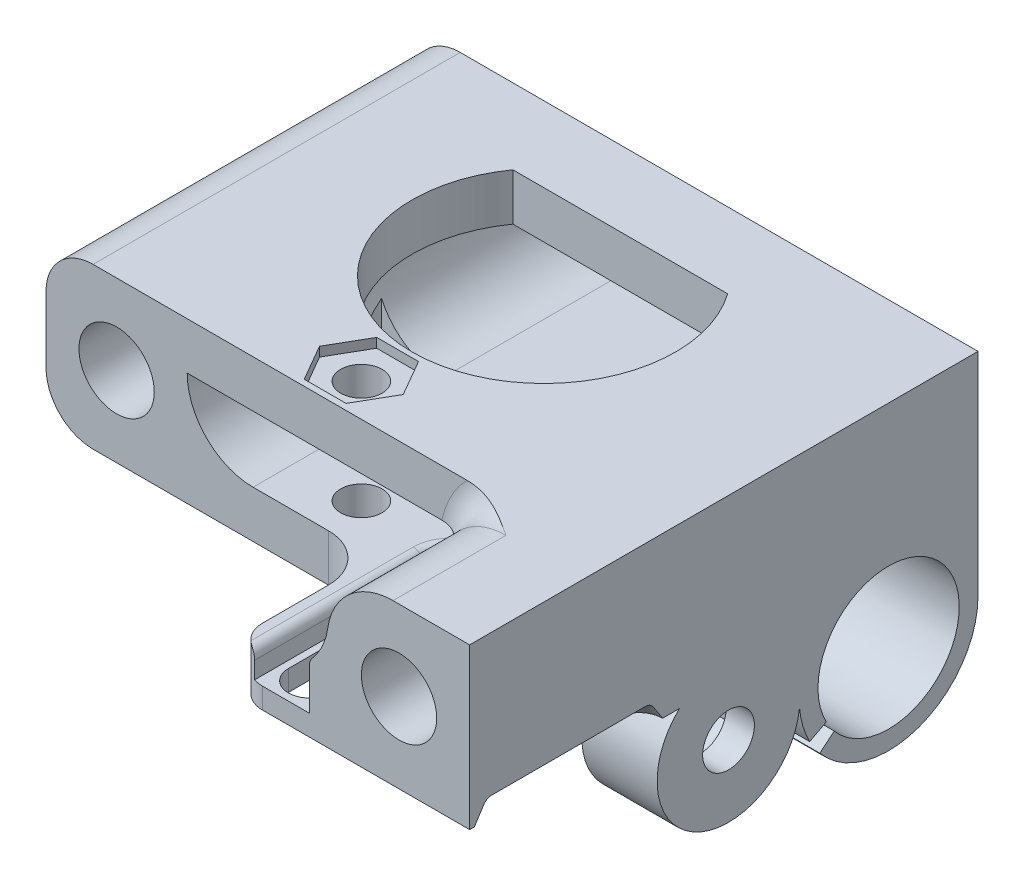
SolidWorks part; units mm, degrees
material "ABS generico"
ref_plane "Front Plane" through (0, 0, 0) normal (0, 0, 1) x (1, 0, 0)
ref_plane "Top Plane" through (0, 0, 0) normal (0, 1, 0) x (1, 0, 0)
ref_plane "Right Plane" through (0, 0, 0) normal (1, 0, 0) x (0, 0, -1)
sketch "Sketch1" plane through (0, 0, 0) normal (1, 0, 0) x (0, 0, -1)
  line L1 (21.1236, -26.9641) -> (22.8813, -26.0274)
  line L3 (23.7305, -27.2923) -> (22.1984, -28.5649)
  line L4 (20.0416, -23.294) -> (20.0416, -17)
  line L8 (39, 0) -> (0, 0)
  line L12 (0, -17) -> (0, 0)
  line L13 (0, -17) -> (20.0416, -17)
  line L15 (39, -22.5) -> (39, 0)
  line L19 (16.5, -29.4282) -> (20.0416, -23.294) construction
  line L20 (8.5, -29.4282) -> (16.5, -29.4282) construction
  line L21 (4.5, -22.5) -> (8.5, -29.4282) construction
  line L22 (4.5, -17) -> (4.5, -22.5) construction
  arc A0 (23.7305, -27.2923) -> (22.8813, -26.0274) centre (29.5041, -22.4988) ccw
  arc A1 (20.0416, -23.294) -> (21.1236, -26.9641) centre (29.5041, -22.4988) ccw
  arc A2 (22.1984, -28.5649) -> (39, -22.5) centre (29.5041, -22.4988) ccw
  circle A5 centre (12.5, -22.5) radius 2.75 construction
  dimension "D2" = 7.5042
  dimension "D3" = 9.4959
  dimension "D1" = 39
  dimension "D4" = 17
extrude "Extrude1" add sketch "Sketch1" against normal blind 60
sketch "Sketch2" plane through (0, 0, 0) normal (0, 0, 1) x (1, 0, 0)
  line L0 (-60, -8.5) -> (0, -8.5) construction
  line L1 (-60, 0) -> (-60, -17) construction
  line L2 (0, 0) -> (0, -17) construction
  line L3 (-30, 1.8171) -> (-30, -40.9837) construction
  line L5 (-15, -12) -> (-45, -12)
  line L6 (-15, -12) -> (-15, -5)
  line L7 (-15, -5) -> (-45, -5)
  line L8 (-45, -12) -> (-45, -5)
  line L9 (-15, -12) -> (-45, -5) construction
  line L10 (-15, -5) -> (-45, -12) construction
  circle A0 centre (-52.5, -8.5) radius 4
  circle A1 centre (-7.5, -8.5) radius 4
  point P12 (-30, -8.5)
  dimension "D1" = 8
  dimension "D2" = 22.5
  dimension "D3" = 7.5
  dimension "D4" = 7
  dimension "D5" = 30
extrude "Extrude2" cut sketch "Sketch2" against normal up to surface (39 mm away) up to face at (-30, -11.25, -39)
sketch "Sketch3" plane through (0, 0, 0) normal (0, 0, 1) x (1, 0, 0)
  line L0 (-52.5, -8.5) -> (-7.5, -8.5) construction
  line L1 (-52.5, -8.5) -> (-52.5, 8.8734) construction
  line L2 (-32.5, -8.5) -> (-32.5, 8.8734) construction
  dimension "D1" = 20
sketch "Sketch4" plane through (0, 0, 0) normal (1, 0, 0) x (0, 0, -1)
  line L0 (7.2804, -17) -> (20.0416, -17)
  line L1 (12.5, -17.9967) -> (8.6, -20.2483) construction
  line L2 (8.6, -20.2483) -> (8.6, -24.7517) construction
  line L3 (8.6, -24.7517) -> (12.5, -27.0033) construction
  line L4 (12.5, -27.0033) -> (16.4, -24.7517) construction
  line L5 (16.4, -24.7517) -> (16.4, -20.2483) construction
  line L6 (16.4, -20.2483) -> (12.5, -17.9967) construction
  line L7 (0, -17) -> (20.0416, -17) construction
  line L8 (20.0416, -17) -> (20.0817, -22.3872)
  circle A0 centre (12.5, -22.5) radius 3.9 construction
  arc A1 (7.2804, -17) -> (20.0817, -22.3872) centre (12.5, -22.5) ccw
  dimension "D1" = 7.8
extrude "Extrude3" add sketch "Sketch4" against normal blind 8
sketch "Sketch5" plane through (0, 0, 0) normal (1, 0, 0) x (0, 0, -1)
  circle A0 centre (12.5, -22.5) radius 2.75
  dimension "D1" = 5.5
extrude "Extrude4" cut sketch "Sketch5" against normal up to surface (8 mm away) up to face at (-8, -22.1484, -14.2839)
sketch "Sketch6" plane through (-8, 0, 0) normal (-1, 0, 0) x (0, 0, 1)
  line L1 (-12.5, -17.8812) -> (-16.5, -20.1906)
  line L2 (-16.5, -20.1906) -> (-16.5, -24.8094)
  line L3 (-16.5, -24.8094) -> (-12.5, -27.1188)
  line L4 (-12.5, -27.1188) -> (-8.5, -24.8094)
  line L5 (-8.5, -24.8094) -> (-8.5, -20.1906)
  line L6 (-8.5, -20.1906) -> (-12.5, -17.8812)
extrude "Extrude5" cut sketch "Sketch6" against normal blind 5
sketch "Sketch7" plane through (0, 0, 0) normal (0, 1, 0) x (1, 0, 0)
  line L2 (-31, -370.8295) -> (-31, 97.9462) construction
  line L6 (-30.9897, -180.6724) -> (-30.9897, -405.4164) construction
  circle A0 centre (-31, 4.5) radius 2.2
extrude "Extrude6" cut sketch "Sketch7" against normal up to surface (17 mm away) up to face at (-22.6667, -17, -9.1073)
sketch "Sketch8" plane through (0, 0, -39) normal (0, 0, -1) x (-1, 0, 0)
  line L0 (7.5, -8.5) -> (52.5, -8.5) construction
  line L1 (30, -8.5) -> (30, 3.0319) construction
  circle A0 centre (7.5, -8.5) radius 4.201
  circle A1 centre (52.5, -8.5) radius 1.25
  circle A2 centre (7.5, -8.5) radius 1.25
  circle A3 centre (52.5, -8.5) radius 4.201
  dimension "D1" = 2.5
extrude "Extrude7" add sketch "Sketch8" against normal blind 5
sketch "Sketch10" plane through (-60, 0, 0) normal (-1, 0, 0) x (0, 0, 1)
  line L1 (-20.0416, -17) -> (-39.247, -17)
  line L2 (-20.0416, -17) -> (-20.0416, -32.1139)
  line L3 (-20.0416, -32.1139) -> (-39.247, -32.1139)
  line L4 (-39.247, -17) -> (-39.247, -32.1139)
extrude "Extrude8" cut sketch "Sketch10" against normal blind 10
fillet "Fillet9" radius 10 2 edges at (-55, -17, -24.3976) (-55, -17, -34.6107)
fillet "Fillet11" radius 5 1 edges at (-60, 0, -19.5)
fillet "Fillet12" radius 5 5 edges at (-60, -17, -38.3198) (-60, -16.7094, -35.2462) (-60, -14.9946, -29.5041) (-60, -16.7094, -23.7621) (-60, -17, -10.6843)
sketch "Sketch12" plane through (0, 0, 0) normal (0, 0, 1) x (1, 0, 0)
  line L0 (-15, -12) -> (-15, 2.5343) construction
  line L1 (0, 0) -> (-20.7492, 0) construction
  line L2 (-55, 0) -> (0, 0) construction
  line L3 (-45, -12) -> (-15, -12) construction
  line L4 (-15, 0) -> (0, 0)
  line L5 (-11.5, -8.5) -> (-11.5, 2.5343) construction
  line L6 (-15, -17) -> (0, -17)
  line L7 (0, 0) -> (0, -17)
  line L8 (-15, -17) -> (-25, -17)
  line L9 (-25, -12) -> (-15, -12)
  line L10 (-15, -12) -> (-15, 0)
  line L11 (-25, -17) -> (-25, -12)
  circle A0 centre (-7.5, -8.5) radius 4
  point P21 (-14.5, -8.5)
  point P22 (-14.5, 2.5343)
  dimension "D3" = 8
  dimension "D1" = 10
extrude "Extrude10" add sketch "Sketch12" along normal blind 15
sketch "Sketch13" plane through (0, -17, 0) normal (0, -1, 0) x (1, 0, 0)
  line L2 (-20, -5.2455) -> (-20, 23.7024) construction
  line L4 (-25, 0) -> (-9.3359, 0) construction
  line L5 (-25, 15) -> (-25, 0) construction
  line L6 (-20, 12) -> (-20, -3) construction
  line L7 (-17.75, 12) -> (-17.75, -3)
  line L8 (-22.25, 12) -> (-22.25, -3)
  line L9 (-25, 15) -> (0, 15) construction
  arc A0 (-17.75, 12) -> (-22.25, 12) centre (-20, 12) ccw
  arc A1 (-22.25, -3) -> (-17.75, -3) centre (-20, -3) ccw
  point P14 (-20, 4.5)
  dimension "D2" = 3
  dimension "D1" = 5
extrude "Extrude11" cut sketch "Sketch13" against normal up to surface (5 mm away) up to face at (-28.8, -12, -4.5)
sketch "Sketch14" plane through (0, -17, 0) normal (0, -1, 0) x (1, 0, 0)
  line L0 (1.5, -3) -> (1.5, 12)
  line L1 (-12, -10.2024) -> (-12, 22.3262) construction
  line L2 (-1.5, 12) -> (-1.5, -3)
  line L3 (-10.5, -3) -> (-10.5, 12)
  line L4 (-13.5, 12) -> (-13.5, -3)
  arc A0 (-1.5, -3) -> (1.5, -3) centre (0, -3) ccw
  arc A1 (1.5, 12) -> (-1.5, 12) centre (0, 12) ccw
  arc A2 (-10.5, 12) -> (-13.5, 12) centre (-12, 12) ccw
  arc A3 (-13.5, -3) -> (-10.5, -3) centre (-12, -3) ccw
extrude "Extrude12" cut sketch "Sketch14" against normal blind 2
chamfer "Chamfer1" distance 1 angle 45 4 edges at (-13.5, -17, 4.5) (-12, -17, -4.5) (-12, -17, 13.5) (-10.5, -17, 4.5)
fillet "Fillet15" radius 3 1 edges at (-25, -14.5, 15)
sketch "Sketch15" plane through (0, 0, 0) normal (0, 1, 0) x (1, 0, 0)
  line L0 (-50, 22.8813) -> (0, 22.8813) construction
  line L1 (-41.4058, 31) -> (-18.5942, 31)
  arc A0 (-41.4058, 31) -> (-18.5942, 31) centre (-30, 22.8813) ccw
extrude "Extrude13" cut sketch "Sketch15" against normal blind 9
fillet "Fillet18" radius 1 4 edges at (-13.5, -15, 4.5) (-12, -15, 13.5) (-10.5, -15, 4.5) (-12, -15, -4.5)
fillet "Fillet19" radius 11 4 edges at (-13.5, -16, 4.5) (-12, -16, 13.5) (-10.5, -16, 4.5) (-12, -16, -4.5)
fillet "Fillet20" radius 7 1 edges at (-45, -12, -19.5)
sketch "Sketch16" plane through (0, -17, 0) normal (0, -1, 0) x (1, 0, 0)
  line L0 (-30, -8.881) -> (-30, -22.8813) construction
  line L1 (-44.4017, -20.0416) -> (-15.5983, -20.0416)
  arc A1 (-15.5983, -20.0416) -> (-44.4017, -20.0416) centre (-30, -22.8813) ccw
extrude "Extrude14" cut sketch "Sketch16" against normal up to surface (12 mm away) up to face at (-30, -5, -19.9405)
fillet "Fillet21" radius 7 1 edges at (-15, -12, -12)
fillet "Fillet22" radius 5 1 edges
sketch "Sketch17" plane through (0, 0, 0) normal (0, 1, 0) x (1, 0, 0)
  line L7 (-35.4444, 4.5) -> (-33.2222, 0.651)
  line L8 (-33.2222, 0.651) -> (-28.7778, 0.651)
  line L9 (-28.7778, 0.651) -> (-26.5556, 4.5)
  line L10 (-26.5556, 4.5) -> (-28.7778, 8.349)
  line L11 (-28.7778, 8.349) -> (-33.2222, 8.349)
  line L12 (-33.2222, 8.349) -> (-35.4444, 4.5)
  circle A0 centre (-31, 4.5) radius 3.849 construction
extrude "Cut-Extrude1" cut sketch "Sketch17" against normal blind 1
sketch "Sketch18" plane through (0, -5, 0) normal (0, -1, 0) x (1, 0, 0)
  line L0 (-20, -5.25) -> (-20, 17.0853) construction
  line L1 (-17, -3) -> (-17, 17.0853)
  line L2 (-23, -3) -> (-23, 17.0853)
  line L3 (-16.6454, -3) -> (-23.5438, -3) construction
  line L4 (-23, 17.0853) -> (-17, 17.0853)
  line L5 (-23, -5.25) -> (-23, 17.0853) construction
  line L6 (-17, -5.25) -> (-17, 17.0853) construction
  arc A0 (-22.25, -3) -> (-17.75, -3) centre (-20, -3) ccw construction
  arc A1 (-23, -3) -> (-17, -3) centre (-20, -3) ccw
  dimension "D1" = 3
  dimension "D2" = 3
extrude "Cut-Extrude2" cut sketch "Sketch18" along normal blind 9.8
fillet "Fillet33" radius 7 1 edges
fillet "Fillet34" radius 3 1 edges at (-12.3269, -1.3875, 0)
chamfer "Chamfer4" distance 1 angle 57 3 edges at (-1.0607, -17, 13.0607) (-1.0607, -17, -4.0607) (-1.5, -17, 4.5) first distance on face at (-22.4282, -17, -3.1966)
fillet "Fillet39" radius 1 3 edges at (-1.0607, -15, 13.0607) (-1.0607, -15, -4.0607) (-1.5, -15, 4.5)
fillet "Fillet40" radius 1 4 edges at (-17, -9.899, 6) (-18.1295, -10.8326, -5.3455) (-22.7386, -12, -4.2247) (-23, -12, 5.9142)
